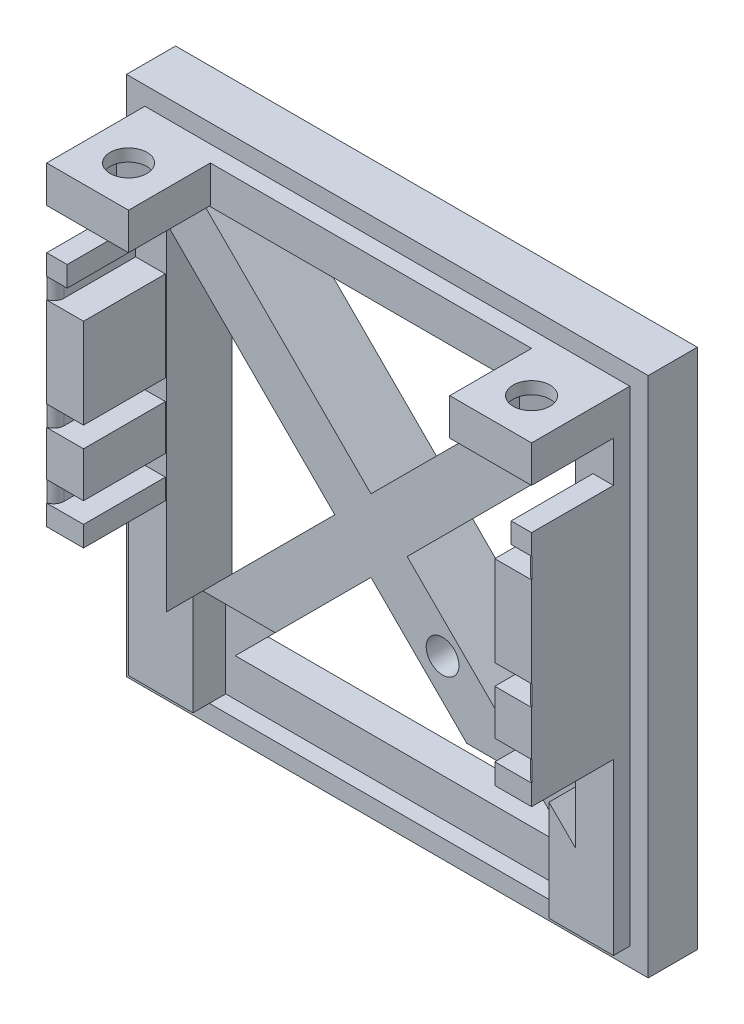
SolidWorks part; units mm, degrees
ref_plane "Plano frontal" through (0, 0, 0) normal (0, 0, 1) x (1, 0, 0)
ref_plane "Plano superior" through (0, 0, 0) normal (0, 1, 0) x (1, 0, 0)
ref_plane "Plano direito" through (0, 0, 0) normal (1, 0, 0) x (0, 0, -1)
sketch "Esboço3" plane through (0, 0, 0) normal (0, 0, 1) x (1, 0, 0)
  line L1 (23.7, 23.7) -> (-23.7, 23.7)
  line L2 (23.7, 23.7) -> (23.7, -23.7)
  line L3 (23.7, -23.7) -> (-23.7, -23.7)
  line L4 (-23.7, 23.7) -> (-23.7, -23.7)
  line L5 (23.7, 23.7) -> (-23.7, -23.7) construction
  line L6 (23.7, -23.7) -> (-23.7, 23.7) construction
  point P0 (0, 0)
  dimension "D1" = 47.4
  dimension "D2" = 47.4
extrude "Ressalto-extrusão2" add sketch "Esboço3" along normal blind 1.6
sketch "Esboço5" plane through (0, 0, 0) normal (0, 0, -1) x (-1, 0, 0)
  line L8 (25.5, -25.5) -> (25.5, 25.5)
  line L9 (25.5, 25.5) -> (-25.5, 25.5)
  line L10 (-25.5, 25.5) -> (-25.5, -25.5)
  line L11 (-25.5, -25.5) -> (25.5, -25.5)
  line L12 (25.5, -25.5) -> (25.5, 25.5)
  line L13 (25.5, 25.5) -> (-25.5, 25.5)
  line L14 (-25.5, 25.5) -> (-25.5, -25.5)
  line L15 (-25.5, -25.5) -> (25.5, -25.5)
  dimension "D1" = 1.8
extrude "Ressalto-extrusão3" add sketch "Esboço5" along normal blind 1.6
sketch "Esboço6" plane through (0, 0, -1.6) normal (0, 0, -1) x (-1, 0, 0)
  line L1 (3.5355, 0) -> (20, 16.4645)
  line L2 (-16.4645, -20) -> (0, -3.5355)
  line L3 (-20, 16.4645) -> (-3.5355, 0)
  line L4 (-20, -16.4645) -> (-3.5355, 0)
  line L5 (-16.4645, 20) -> (0, 3.5355)
  line L7 (16.4645, 20) -> (-16.4645, 20)
  line L8 (20, 16.4645) -> (20, -16.4645)
  line L9 (16.4645, -20) -> (-16.4645, -20)
  line L10 (-20, 16.4645) -> (-20, -16.4645)
  line L13 (3.5355, 0) -> (20, -16.4645)
  line L15 (0, 3.5355) -> (16.4645, 20)
  line L22 (0, -3.5355) -> (16.4645, -20)
  point P16 (0, 0)
extrude "Corte-extrusão1" cut sketch "Esboço6" against normal up to surface (3.2 mm away) up to face at (0, 0, 1.6)
sketch "Esboço7" plane through (0, 0, 1.6) normal (0, 0, 1) x (1, 0, 0)
  line L4 (-23.7, 23.7) -> (-23.7, -23.7)
  line L5 (-23.7, -23.7) -> (23.7, -23.7)
  line L6 (23.7, -23.7) -> (23.7, 23.7)
  line L7 (23.7, 23.7) -> (-23.7, 23.7)
  line L8 (-23.7, 16.1) -> (-23.7, -7.1)
  line L15 (-23.7, 23.7) -> (-15.7, 23.7)
  line L16 (-23.7, 23.7) -> (-23.7, 20.1)
  line L19 (-23.7, 20.1) -> (-15.7, 20.1)
  line L20 (-15.7, 23.7) -> (-15.7, 20.1)
  line L22 (-21.7, 14.1) -> (-23, 14.1)
  line L23 (-23, 14.1) -> (-23, 12.1)
  line L24 (-23, 12.1) -> (-20.1, 12.1)
  line L25 (23.7, 23.7) -> (-23.7, 23.7) construction
  line L26 (0, 0) -> (0, 31.8693) construction
  line L27 (-20.1, 3.3) -> (-23, 3.3)
  line L28 (-23, 3.3) -> (-23, 1.3)
  line L29 (-23, 1.3) -> (-20.1, 1.3)
  line L30 (-20.1, -3.1) -> (-23, -3.1)
  line L31 (-23, -3.1) -> (-23, -5.1)
  line L32 (-23, -5.1) -> (-20.1, -5.1)
  line L35 (-23.7, -7.1) -> (-20.1, -7.1)
  line L36 (-20.1, -7.1) -> (-20.1, -5.1)
  line L39 (-20.1, 12.1) -> (-20.1, 3.3)
  line L40 (-20.1, 1.3) -> (-20.1, -3.1)
  line L45 (-21.7, 16.1) -> (-23.7, 16.1)
  line L46 (-21.7, 16.1) -> (-21.7, 14.1)
  point P10 (-23, 13.1)
  point P23 (-21.55, 1.3)
  dimension "D3" = 2
  dimension "D4" = 23
  dimension "D5" = 9.6
  dimension "D6" = 8.8
  dimension "D7" = 2
  dimension "D8" = 23
  dimension "D9" = 4.4
  dimension "D10" = 2
  dimension "D11" = 23
  dimension "D12" = 2
  dimension "D13" = 2
  dimension "D2" = 2
  dimension "D14" = 8
  dimension "D15" = 3.6
  dimension "D1" = 0
extrude "Ressalto-extrusão4" add sketch "Esboço7" along normal blind 8
mirror "Espelhar1" about plane through (0, 0, 0) normal (1, 0, 0) of "Ressalto-extrusão4"
fillet "Filete1" radius 1 6 edges at (23, 13.1, 9.6) (23, 2.3, 9.6) (23, -4.1, 9.6) (-23, -4.1, 9.6) (-23, 13.1, 9.6) (-23, 2.3, 9.6)
sketch "Esboço8" plane through (0, 0, -1.6) normal (0, 0, -1) x (-1, 0, 0)
  line L0 (-16.4645, -20) -> (16.4645, -20) construction
  line L1 (-20, -16.4645) -> (-3.5355, 0) construction
  line L2 (0, -3.5355) -> (-16.4645, -20) construction
  line L3 (16.4645, -20) -> (0, -3.5355) construction
  line L4 (-25.5, -25.5) -> (25.5, -25.5)
  line L5 (25.5, -25.5) -> (25.5, 25.5)
  line L6 (25.5, 25.5) -> (-25.5, 25.5)
  line L7 (-25.5, 25.5) -> (-25.5, -25.5)
  line L8 (-25.5, -25.5) -> (25.5, -25.5)
  line L9 (25.5, -25.5) -> (25.5, 25.5)
  line L10 (25.5, 25.5) -> (-25.5, 25.5)
  line L11 (-25.5, 25.5) -> (-25.5, -25.5)
  line L12 (3.5355, 0) -> (20, -16.4645) construction
  line L13 (20, -16.4645) -> (20, 16.4645) construction
  line L14 (20, 16.4645) -> (3.5355, 0) construction
  line L15 (0, 3.5355) -> (16.4645, 20) construction
  line L16 (16.4645, 20) -> (-16.4645, 20) construction
  line L17 (-20, 16.4645) -> (-20, -16.4645) construction
  line L18 (-16.4645, 20) -> (0, 3.5355) construction
  line L19 (-3.5355, 0) -> (-20, 16.4645) construction
  line L20 (-16.4645, -20) -> (16.4645, -20)
  line L21 (-20, -16.4645) -> (-3.5355, 0)
  line L22 (0, -3.5355) -> (-16.4645, -20)
  line L23 (16.4645, -20) -> (0, -3.5355)
  line L24 (3.5355, 0) -> (20, -16.4645)
  line L25 (20, -16.4645) -> (20, 16.4645)
  line L26 (20, 16.4645) -> (3.5355, 0)
  line L27 (0, 3.5355) -> (16.4645, 20)
  line L28 (16.4645, 20) -> (-16.4645, 20)
  line L29 (-20, 16.4645) -> (-20, -16.4645)
  line L30 (-16.4645, 20) -> (0, 3.5355)
  line L31 (-3.5355, 0) -> (-20, 16.4645)
  dimension "D1" = 0
extrude "Ressalto-extrusão5" add sketch "Esboço8" along normal blind 3.2
sketch "Esboço9" plane through (0, 0, 1.6) normal (0, 0, 1) x (1, 0, 0)
  line L0 (0, 0) -> (0, -30.6057) construction
  line L1 (-23.7, -23.7) -> (23.7, -23.7) construction
  line L2 (17.4, -12.9) -> (-17.4, -12.9)
  line L3 (17.4, -12.9) -> (17.4, -23.7)
  line L4 (17.4, -23.7) -> (-17.4, -23.7)
  line L5 (-17.4, -12.9) -> (-17.4, -23.7)
  line L6 (17.4, -12.9) -> (-17.4, -23.7) construction
  line L7 (17.4, -23.7) -> (-17.4, -12.9) construction
  point P3 (0, -18.3)
  dimension "D1" = 34.8
  dimension "D2" = 10.8
extrude "Corte-extrusão2" cut sketch "Esboço9" against normal blind 3.2
sketch "Esboço10" plane through (0, 0, 1.6) normal (0, 0, 1) x (1, 0, 0)
  line L0 (20.1, -5.1) -> (-34.3608, -5.1) construction
  line L1 (23, -5.1) -> (23, -3.1) construction
  circle A0 centre (7, -6.7) radius 1.6
  point P7 (23, -4.1)
  dimension "D1" = 3.2
  dimension "D2" = 16
extrude "Corte-extrusão3" cut sketch "Esboço10" against normal through all
sketch "Esboço11" plane through (0, 20.1, 0) normal (0, -1, 0) x (1, 0, 0)
  line L0 (-15.7, 5.6) -> (-23.7, 5.6) construction
  line L1 (-15.7, 9.6) -> (-15.7, 1.6) construction
  line L2 (-23.7, 9.6) -> (-23.7, 1.6) construction
  line L3 (-19.7, 9.6) -> (-19.7, 1.6) construction
  line L4 (-23.7, 9.6) -> (-15.7, 9.6) construction
  line L5 (-23.7, 1.6) -> (-15.7, 1.6) construction
  line L7 (-19.7, 8.8332) -> (-22.5, 7.2166)
  line L8 (-22.5, 7.2166) -> (-22.5, 3.9834)
  line L9 (-22.5, 3.9834) -> (-19.7, 2.3668)
  line L10 (-19.7, 2.3668) -> (-16.9, 3.9834)
  line L11 (-16.9, 3.9834) -> (-16.9, 7.2166)
  line L12 (-16.9, 7.2166) -> (-19.7, 8.8332)
  circle A0 centre (-19.7, 5.6) radius 2.8 construction
  circle A1 centre (-19.7, 5.6) radius 1.8
  dimension "D2" = 3.6
  dimension "D1" = 5.6
extrude "Corte-extrusão4" cut sketch "Esboço11" against normal blind 2.4
extrude "Corte-extrusão5" cut sketch "Esboço11<2>" against normal through all contours A1 region at (-19.7, 20.1, 5.6)
sketch "Esboço11<2>" plane through (0, 20.1, 0) normal (0, -1, 0) x (1, 0, 0) same geometry as "Esboço11"
mirror "Espelhar2" about plane through (0, 0, 0) normal (1, 0, 0) of "Corte-extrusão4", "Corte-extrusão5"
